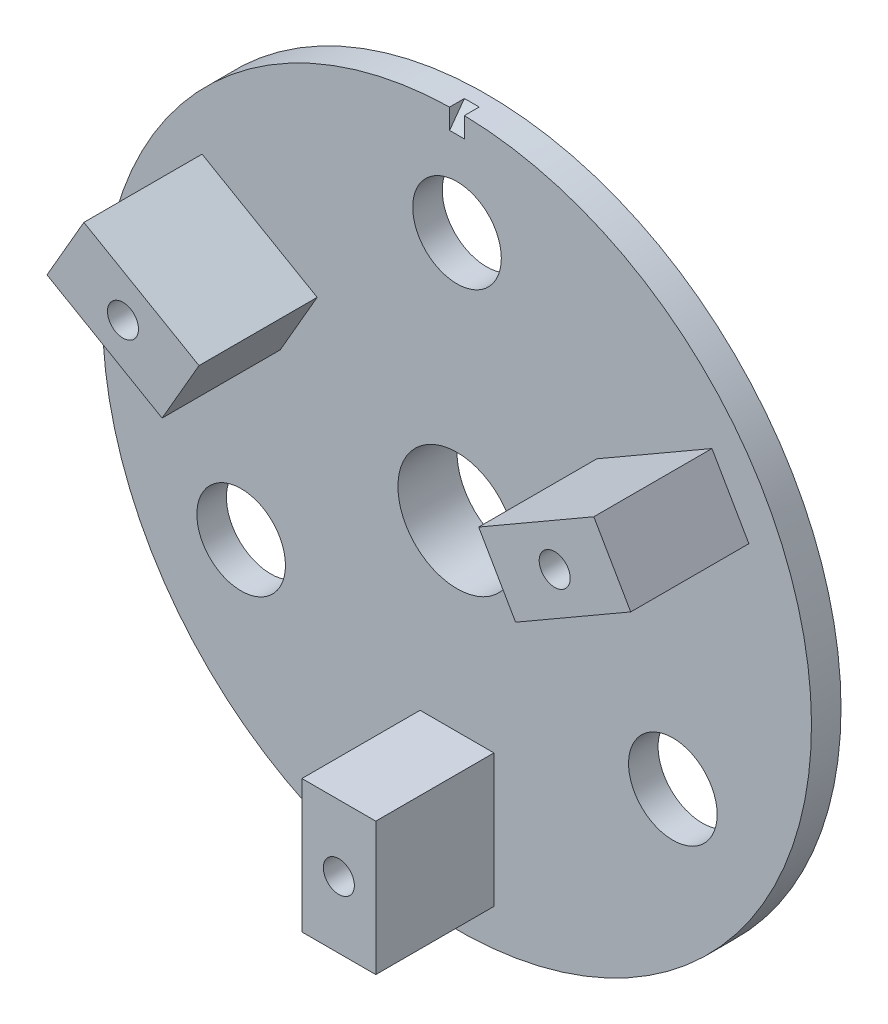
SolidWorks part; units mm, degrees
material "1.7225 (42CrMo4)"
ref_plane "Front Plane" through (0, 0, 0) normal (0, 0, 1) x (1, 0, 0)
ref_plane "Top Plane" through (0, 0, 0) normal (0, 1, 0) x (1, 0, 0)
ref_plane "Right Plane" through (0, 0, 0) normal (1, 0, 0) x (0, 0, -1)
sketch "Sketch1" plane through (0, 0, 0) normal (0, 0, 1) x (1, 0, 0)
  circle A0 centre (0, 0) radius 48
  circle A1 centre (0, 0) radius 8
  dimension "D1" = 96
  dimension "D2" = 16
extrude "EX_Carrier_Front_Plate_4mm" add sketch "Sketch1" along normal mid plane 4
sketch "Sketch2" plane through (0, 0, 2) normal (0, 0, 1) x (1, 0, 0)
  line L0 (0, 0) -> (0, 33.75) construction
  circle A0 centre (0, 33.75) radius 6
  dimension "D2" = 12
  dimension "D1" = 33.75
extrude "CUT_Pin_Hole_Ø12" cut sketch "Sketch2" against normal through all both and the other way through all contours A0
pattern_circular "PAT_Pin_Holes_3x120" count 3 over 360 about axis through (0, 0, 2) along (0, 0, 1) of "CUT_Pin_Hole_Ø12"
sketch "Sketch3" plane through (0, 0, 2) normal (0, 0, 1) x (1, 0, 0)
  line L0 (-29.2284, -30.875) -> (29.2284, -30.875)
  line L1 (-41.3527, -9.875) -> (-12.1244, 40.75)
  line L2 (12.1244, 40.75) -> (41.3527, -9.875)
  circle A10 centre (-29.2284, -16.875) radius 14
  arc A11 (-41.3527, -9.875) -> (-29.2284, -30.875) centre (-29.2284, -16.875) ccw
  circle A13 centre (0, 33.75) radius 14
  arc A14 (12.1244, 40.75) -> (-12.1244, 40.75) centre (0, 33.75) ccw
  circle A16 centre (29.2284, -16.875) radius 14
  arc A17 (29.2284, -30.875) -> (41.3527, -9.875) centre (29.2284, -16.875) ccw
  circle M10 centre (0, 0) radius 48
  dimension "D1" = 8
  dimension "D2" = 8
  dimension "D3" = 8
extrude "Cut-Extrude1" [suppressed] cut sketch "Sketch3" against normal through all both and the other way through all contours A17 L0 A11 L1 A14 L2 M10
sketch "Sketch4" plane through (0, 0, 0) normal (1, 0, 0) x (0, 0, -1)
  line L0 (-2, 45.2477) -> (0, 48)
  line L1 (-2, 48) -> (-2, -48) construction
  line L2 (2, 48) -> (-2, 48) construction
  line L3 (0, 48) -> (-2, 48)
  line L4 (-2, 48) -> (-2, 45.2477)
extrude "Cut-Extrude2" cut sketch "Sketch4" against normal mid plane 2
sketch "Sketch5" plane through (0, 0, 0) normal (1, 0, 0) x (0, 0, -1)
  line L0 (1.5, 8) -> (1.5, 13)
  line L1 (1.5, 13) -> (6, 13)
  line L2 (6, 13) -> (6, 8)
  line L3 (6, 8) -> (1.5, 8)
  line L4 (0, 0) -> (4, 0) construction
revolve "Revolve1" add sketch "Sketch5" angle 360 about L4
ref_axis "Axis1" through (0, 0, -6.4083) along (0, 0, 1)
sketch "Sketch6" plane through (0, 0, 0) normal (0, 0, 1) x (1, 0, 0)
  line L0 (-5, -24.75) -> (5, -24.75)
  line L1 (5, -24.75) -> (5, -42.75)
  line L2 (5, -42.75) -> (-5, -42.75)
  line L3 (-5, -42.75) -> (-5, -24.75)
extrude "Boss-Extrude1" add sketch "Sketch6" along normal blind 18
sketch "Sketch7" plane through (0, 0, 18) normal (0, 0, 1) x (1, 0, 0)
  circle A0 centre (0, -33.75) radius 2.1
extrude "Cut-Extrude4" cut sketch "Sketch7" against normal blind 12
pattern_circular "CirPattern1" count 3 over 360 about axis through (0, 0, -6.4083) along (0, 0, 1) of "Boss-Extrude1"
pattern_circular "CirPattern2" count 3 over 360 about axis through (0, 0, -6.4083) along (0, 0, 1) of "Cut-Extrude4"
